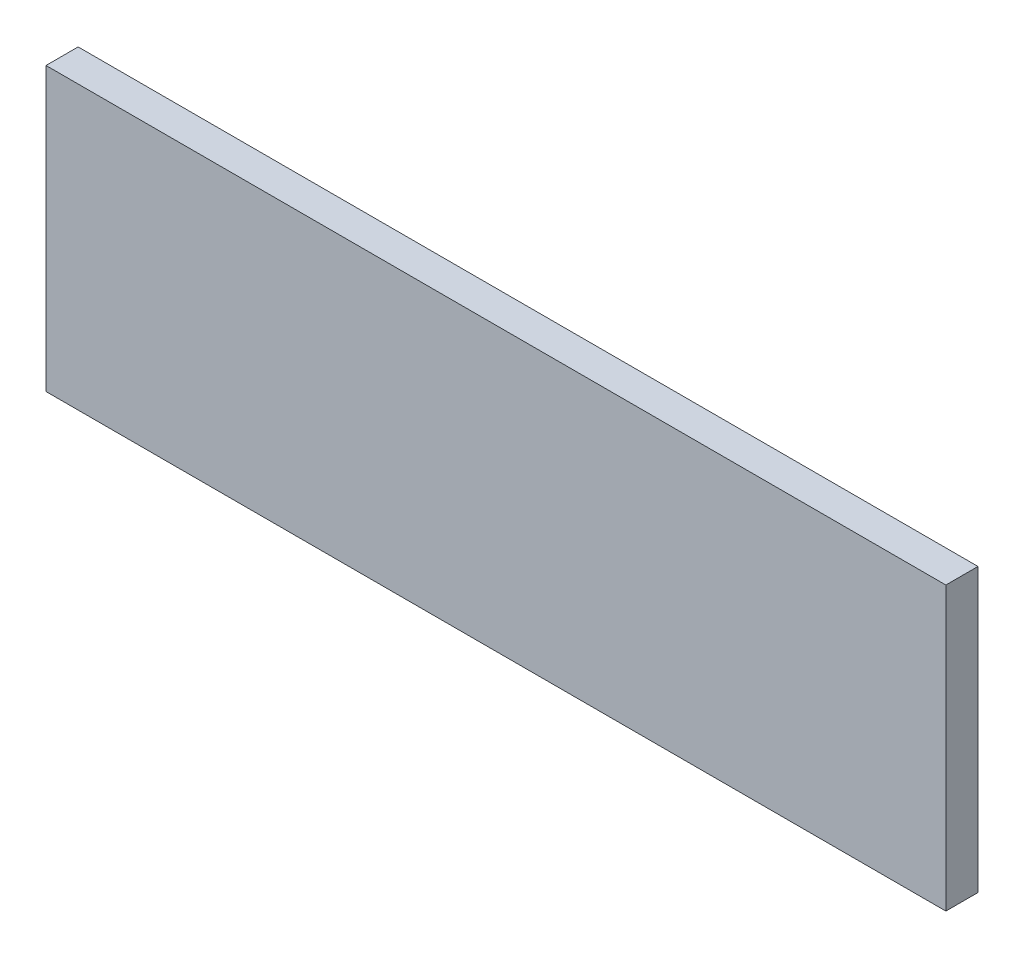
SolidWorks part; units mm, degrees
ref_plane "XY" through (0, 0, 0) normal (0, 0, 1) x (1, 0, 0)
ref_plane "XZ" through (0, 0, 0) normal (0, 1, 0) x (1, 0, 0)
ref_plane "YZ" through (0, 0, 0) normal (1, 0, 0) x (0, 0, -1)
ref_axis "X" through (-88.99, 0, 0) along (1, 0, 0)
ref_axis "Y" through (0, -55, 0) along (0, 1, 0)
ref_axis "Z" through (0, 0, 55) along (0, 0, -1)
sketch "Sketch1" plane through (0, 0, 0) normal (0, 0, 1) x (1, 0, 0)
  line L1 (-88.9, -27.9) -> (88.9, -27.9)
  line L2 (-88.9, -27.9) -> (-88.9, 27.9)
  line L3 (-88.9, 27.9) -> (88.9, 27.9)
  line L4 (88.9, -27.9) -> (88.9, 27.9)
  line L5 (-88.9, -27.9) -> (88.9, 27.9) construction
  line L6 (-88.9, 27.9) -> (88.9, -27.9) construction
  point P0 (0, 0)
  dimension "D1" = 55.8
  dimension "D2" = 177.8
extrude "Boss-Extrude1" add sketch "Sketch1" along normal mid plane 6.35
